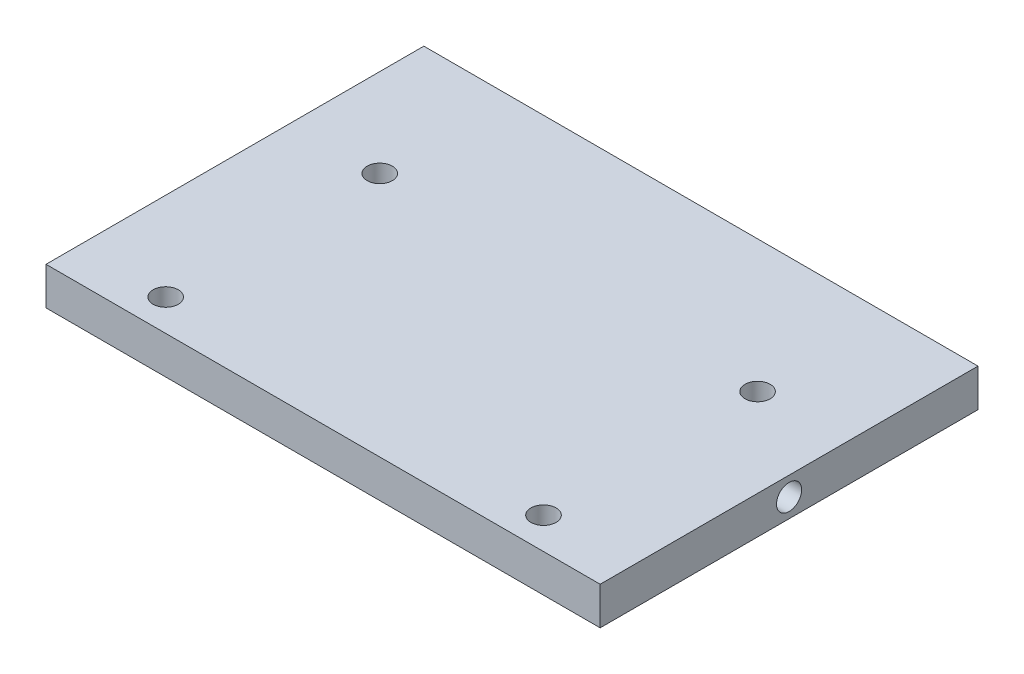
SolidWorks part; units mm, degrees
ref_plane "Front Plane" through (0, 0, 0) normal (0, 0, 1) x (1, 0, 0)
ref_plane "Top Plane" through (0, 0, 0) normal (0, 1, 0) x (1, 0, 0)
ref_plane "Right Plane" through (0, 0, 0) normal (1, 0, 0) x (0, 0, -1)
sketch "Sketch1" plane through (0, 0, 0) normal (0, 1, 0) x (1, 0, 0)
  line L1 (-22, 15) -> (22, 15)
  line L2 (-22, 15) -> (-22, -15)
  line L3 (-22, -15) -> (22, -15)
  line L4 (22, 15) -> (22, -15)
  line L5 (-22, 15) -> (22, -15) construction
  line L6 (-22, -15) -> (22, 15) construction
  point P0 (0, 0)
  dimension "D1" = 44
  dimension "D2" = 30
extrude "Boss-Extrude1" add sketch "Sketch1" along normal blind 3 contours L1 L4 L3 L2
sketch "Sketch2" plane through (-22, 0, 0) normal (-1, 0, 0) x (0, 0, 1)
  line L0 (-15, 1.5) -> (15, 1.5) construction
  line L1 (-15, 3) -> (-15, 0) construction
  line L2 (15, 3) -> (15, 0) construction
  circle A0 centre (0, 1.5) radius 1
  dimension "D1" = 2
extrude "Cut-Extrude1" cut sketch "Sketch2" against normal blind 5
mirror "Mirror1" about plane through (0, 0, 0) normal (1, 0, 0) of "Cut-Extrude1"
sketch "Sketch3" plane through (0, 0, 0) normal (0, -1, 0) x (-1, 0, 0)
  line L1 (-15, 4.5) -> (15, 4.5) construction
  line L2 (-15, -12.5) -> (15, -12.5) construction
  line L3 (0, 15) -> (0, -15) construction
  line L4 (22, 15) -> (-22, 15) construction
  line L5 (22, -15) -> (-22, -15) construction
  circle A0 centre (15, 4.5) radius 1
  circle A1 centre (15, -12.5) radius 1
  circle A2 centre (-15, -12.5) radius 1
  circle A3 centre (-15, 4.5) radius 1
  point P18 (0, 4.5)
  dimension "D3" = 2
  dimension "D4" = 2
  dimension "D5" = 2
  dimension "D6" = 2
  dimension "D1" = 30
  dimension "D2" = 17
  dimension "D7" = 2.5
extrude "Cut-Extrude2" cut sketch "Sketch3" against normal blind 5
